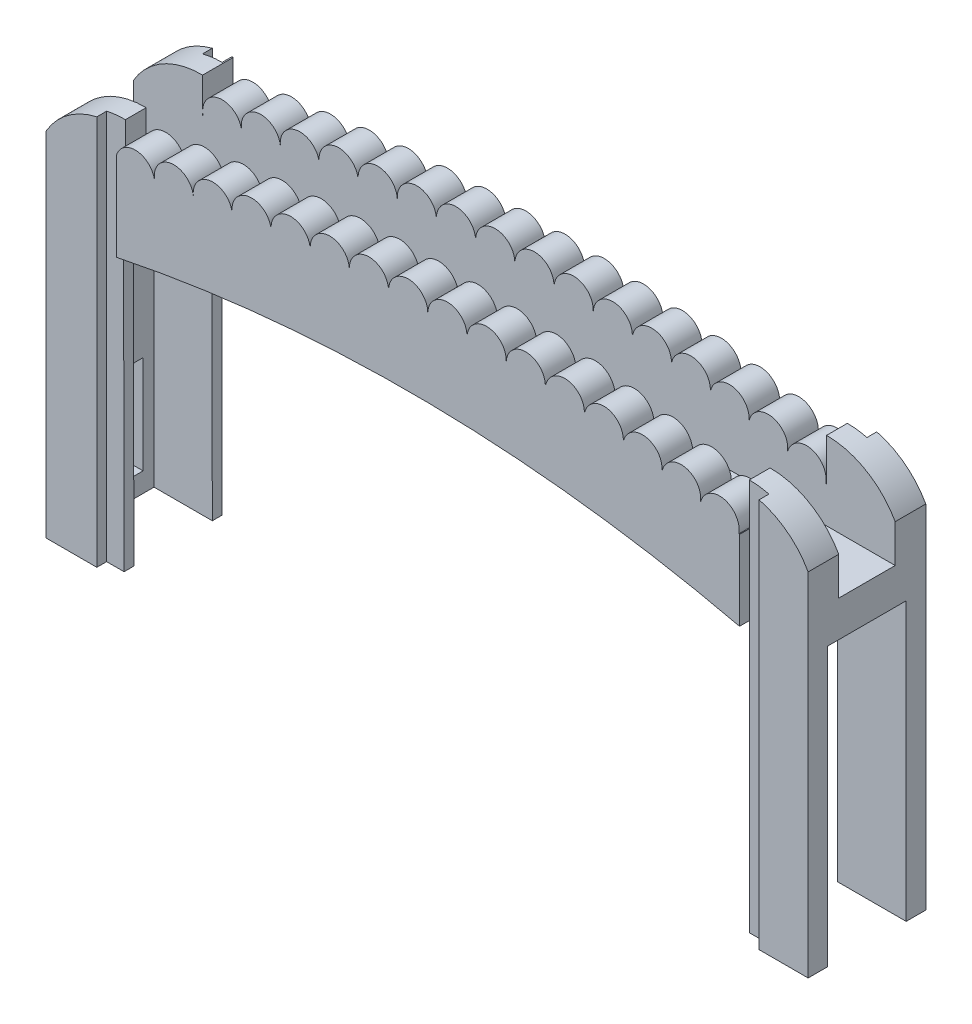
SolidWorks part; units mm, degrees
material "PVC 0.007 Plasticized"
ref_plane "Front Plane" through (0, 0, 0) normal (0, 0, 1) x (1, 0, 0)
ref_plane "Top Plane" through (0, 0, 0) normal (0, 1, 0) x (1, 0, 0)
ref_plane "Right Plane" through (0, 0, 0) normal (1, 0, 0) x (0, 0, -1)
ref_axis "X-Axis" through (-88.99, 0, 0) along (1, 0, 0)
ref_axis "Y-Axis" through (0, 55, 0) along (0, -1, 0)
ref_axis "Z-Axis" through (0, 0, 55) along (0, 0, -1)
sketch "Sketch1" plane through (0, 0, 0) normal (0, 0, 1) x (1, 0, 0)
  line L0 (25.2235, -24.9543) -> (31.5735, -24.9543)
  line L1 (31.5735, -24.9543) -> (31.5735, 0.4457)
  line L2 (25.2235, 6.7957) -> (25.2235, 3.3687)
  line L3 (25.2235, -24.9543) -> (25.2235, -3.0716)
  line L5 (0.0026, 6.4934) -> (0.2298, 25.4294) construction
  line L6 (-25.2973, 6.7948) -> (-25.2973, 3.9727)
  line L9 (-25.4, -24.9543) -> (-25.4407, -2.4636)
  line L10 (-25.4, -24.9543) -> (-31.7044, -24.9543)
  line L12 (-31.7044, 1.2051) -> (-31.7044, -24.9543)
  arc A0 (31.5735, 0.4457) -> (25.2235, 6.7957) centre (25.2235, 0.4457) ccw
  arc A3 (3.1579, 6.1919) -> (-0.0159, 6.2703) centre (1.5715, 6.2515) ccw
  arc A4 (9.4941, 5.7905) -> (6.3286, 6.0319) centre (7.9129, 5.9315) ccw
  arc A5 (12.6524, 5.4678) -> (9.4941, 5.7905) centre (11.0754, 5.6495) ccw
  arc A6 (15.8139, 5.1861) -> (12.6524, 5.4678) centre (14.2295, 5.2862) ccw
  arc A7 (18.9297, 4.5814) -> (15.8139, 5.1861) centre (17.364, 4.8435) ccw
  arc A8 (22.0499, 3.9975) -> (18.9297, 4.5814) centre (20.4954, 4.3194) ccw
  arc A9 (25.1645, 3.3818) -> (22.0499, 3.9975) centre (23.6044, 3.6756) ccw
  arc A10 (6.3286, 6.0319) -> (3.1579, 6.1919) centre (4.7443, 6.1323) ccw
  arc A11 (-3.1906, 6.2673) -> (-0.0159, 6.2703) centre (-1.6033, 6.2892) cw
  arc A12 (-6.3642, 6.1826) -> (-3.1906, 6.2673) centre (-4.778, 6.2453) cw
  arc A13 (-9.5346, 6.0164) -> (-6.3642, 6.1826) centre (-7.9505, 6.1199) cw
  arc A14 (-12.6997, 5.7689) -> (-9.5346, 6.0164) centre (-11.1187, 5.913) cw
  arc A15 (-15.8519, 5.3981) -> (-12.6997, 5.7689) centre (-14.2806, 5.6247) cw
  arc A16 (-19, 4.9882) -> (-15.8519, 5.3981) centre (-17.4231, 5.1714) cw
  arc A17 (-22.142, 4.5397) -> (-19, 4.9882) centre (-20.5769, 4.8051) cw
  arc A18 (-25.2669, 3.9787) -> (-22.142, 4.5397) centre (-23.7072, 4.2742) cw
  arc A19 (-31.7044, 1.2051) -> (-25.2973, 6.7948) centre (-25.4, 0.4457) cw
  arc A20 (-25.2973, 3.9727) -> (-25.2669, 3.9787) centre (-1.4828, -117.2774) cw
  arc A22 (-25.4407, -2.4636) -> (25.2235, -3.0716) centre (-1.4828, -117.2774) cw
  arc A37 (25.1645, 3.3818) -> (25.2235, 3.3687) centre (-1.4828, -117.2774) cw
  dimension "D4" = 3.175
  dimension "D6" = 3.175
  dimension "D1" = 31.75
  dimension "D2" = 6.35
extrude "Boss-Extrude1" add sketch "Sketch1" against normal blind 12.7
sketch "Sketch3" plane through (0, 0, 0) normal (1, 0, 0) x (0, 0, -1)
  line L0 (12.7, 0.4457) -> (0, 0.4457) construction
  line L1 (4.0652, 0.4457) -> (8.6348, 0.4457)
  line L2 (4.0652, 0.4457) -> (4.0652, 13.0566)
  line L3 (4.0652, 13.0566) -> (8.6348, 13.0566)
  line L4 (8.6348, 0.4457) -> (8.6348, 13.0566)
  line L6 (6.35, 31.4165) -> (6.35, -30.5252) construction
  line L7 (12.7, -24.9543) -> (12.7, 0.4457) construction
  point P10 (6.35, 0.4457)
  dimension "D1" = 6.35
extrude "Cut-Extrude1" cut sketch "Sketch3" against normal through all both and the other way through all
sketch "Sketch4" plane through (31.5735, 0, 0) normal (1, 0, 0) x (0, 0, -1)
  line L0 (4.0652, 0.4457) -> (4.0652, 6.7957) construction
  line L1 (4.0652, -15.4293) -> (8.6348, -15.4293)
  line L2 (4.0652, -15.4293) -> (4.0652, -23.3668)
  line L3 (4.0652, -23.3668) -> (8.6348, -23.3668)
  line L4 (8.6348, -15.4293) -> (8.6348, -23.3668)
  line L5 (8.6348, 6.7957) -> (8.6348, 0.4457) construction
  line L6 (12.7, -24.9543) -> (0, -24.9543) construction
  dimension "D1" = 1.5875
  dimension "D2" = 9.525
extrude "Cut-Extrude2" cut sketch "Sketch4" against normal blind 66.04
sketch "Sketch5" plane through (0, 0, 0) normal (1, 0, 0) x (0, 0, -1)
  line L0 (0, -24.9543) -> (0, 0.4457) construction
  line L1 (0, -24.9543) -> (1.5875, -24.9543)
  line L2 (0, -24.9543) -> (0, 14.7716)
  line L3 (0, 14.7716) -> (1.5875, 14.7716)
  line L4 (1.5875, -24.9543) -> (1.5875, 14.7716)
  line L6 (12.7, -24.9543) -> (11.1125, -24.9543)
  line L7 (12.7, -24.9543) -> (12.7, 14.7716)
  line L8 (12.7, 14.7716) -> (11.1125, 14.7716)
  line L9 (11.1125, -24.9543) -> (11.1125, 14.7716)
  dimension "D1" = 1.5875
  dimension "D2" = 1.5875
extrude "Cut-Extrude3" cut sketch "Sketch5" against normal through all both and the other way through all
sketch "Sketch6" plane through (0, 0, -1.5875) normal (0, 0, 1) x (1, 0, 0)
  line L0 (0, 16.1676) -> (0, -24.1261) construction
  line L1 (25.2235, -24.9543) -> (31.5735, -24.9543) construction
  line L2 (26.811, -24.9543) -> (25.2235, -24.9543)
  line L3 (26.811, -24.9543) -> (26.811, 15.4607)
  line L4 (26.811, 15.4607) -> (25.2235, 15.4607)
  line L5 (25.2235, -24.9543) -> (25.2235, 15.4607)
  line L6 (-26.811, 15.4607) -> (-25.2235, 15.4607)
  line L7 (-25.2235, -24.9543) -> (-25.2235, 15.4607)
  line L8 (-26.811, -24.9543) -> (-25.2235, -24.9543)
  line L9 (-26.811, -24.9543) -> (-26.811, 15.4607)
  dimension "D1" = 1.5875
extrude "Cut-Extrude4" cut sketch "Sketch6" against normal blind 0.7937
sketch "Sketch7" plane through (0, 0, -11.1125) normal (0, 0, -1) x (-1, 0, 0)
  line L0 (0, 0) -> (0, 15.4607) construction
  line L1 (0, 15.4607) -> (0, -21.2985) construction
  line L2 (25.4407, -2.4636) -> (25.4, -24.9543) construction
  line L3 (25.4, -24.9543) -> (26.9875, -24.9543)
  line L4 (25.4, -24.9543) -> (25.4, 13.7642)
  line L5 (25.4, 13.7642) -> (26.9875, 13.7642)
  line L6 (26.9875, -24.9543) -> (26.9875, 13.7642)
  line L7 (31.7044, -24.9543) -> (25.4, -24.9543) construction
  line L9 (-25.2235, -24.9543) -> (-26.811, -24.9543)
  line L10 (-25.2235, -24.9543) -> (-25.2235, 14.7538)
  line L11 (-25.2235, 14.7538) -> (-26.811, 14.7538)
  line L12 (-26.811, -24.9543) -> (-26.811, 14.7538)
  dimension "D1" = 1.5875
  dimension "D2" = 1.5875
extrude "Cut-Extrude5" cut sketch "Sketch7" against normal blind 0.7937
sketch "Sketch8" plane through (-25.445, -0.046, 0) normal (1, 0.0018, 0) x (0, 0, -1)
  line L3 (3.175, -24.9084) -> (9.525, -24.9084)
  line L9 (9.525, -2.4176) -> (3.175, -2.4176)
  line L10 (3.175, -2.4176) -> (3.175, -24.9084)
  line L11 (9.525, -2.4176) -> (9.525, -24.9084)
extrude "Cut-Extrude6" cut sketch "Sketch8" against normal offset from surface (4.6763 mm away) 1.5875 up to face at (-31.7044, -5.5246, -6.35)
sketch "Sketch9" plane through (25.2235, 0, 0) normal (-1, 0, 0) x (0, 0, 1)
  line L1 (-9.525, -24.9543) -> (-3.175, -24.9543)
  line L2 (-9.525, -24.9543) -> (-9.525, -2.4721)
  line L3 (-9.525, -2.4721) -> (-3.175, -2.4721)
  line L4 (-3.175, -24.9543) -> (-3.175, -2.4721)
extrude "Cut-Extrude7" cut sketch "Sketch9" against normal offset from surface (5.5563 mm away) 0.7937 up to face at (31.5735, -8.021, -6.35)
sketch "Sketch10" plane through (0, 0, 0) normal (0, 0, 1) x (1, 0, 0)
  line L0 (-31.7044, -24.9543) -> (-31.7044, 1.2051) construction
  line L2 (-31.7044, -24.6917) -> (-31.7044, 9.3813)
  line L3 (-31.7044, 9.3813) -> (-30.9107, 9.3813)
  line L4 (-30.9107, -24.6917) -> (-30.9107, 9.3813)
  line L5 (-30.9107, -24.6917) -> (-30.9107, -24.9543)
  line L6 (31.5735, -24.9543) -> (30.7797, -24.9543)
  line L7 (31.5735, -24.9543) -> (31.5735, 11.9262)
  line L8 (31.5735, 11.9262) -> (30.7797, 11.9262)
  line L9 (30.7797, -24.9543) -> (30.7797, 11.9262)
  line L10 (-31.7044, -24.9543) -> (-26.811, -24.9543) construction
  line L11 (-30.9107, -24.9543) -> (-31.7044, -24.9543)
  line L12 (-31.7044, -24.9543) -> (-31.7044, -24.6917)
  dimension "D1" = 0.7937
  dimension "D2" = 0.7937
extrude "Cut-Extrude8" cut sketch "Sketch10" against normal through all
